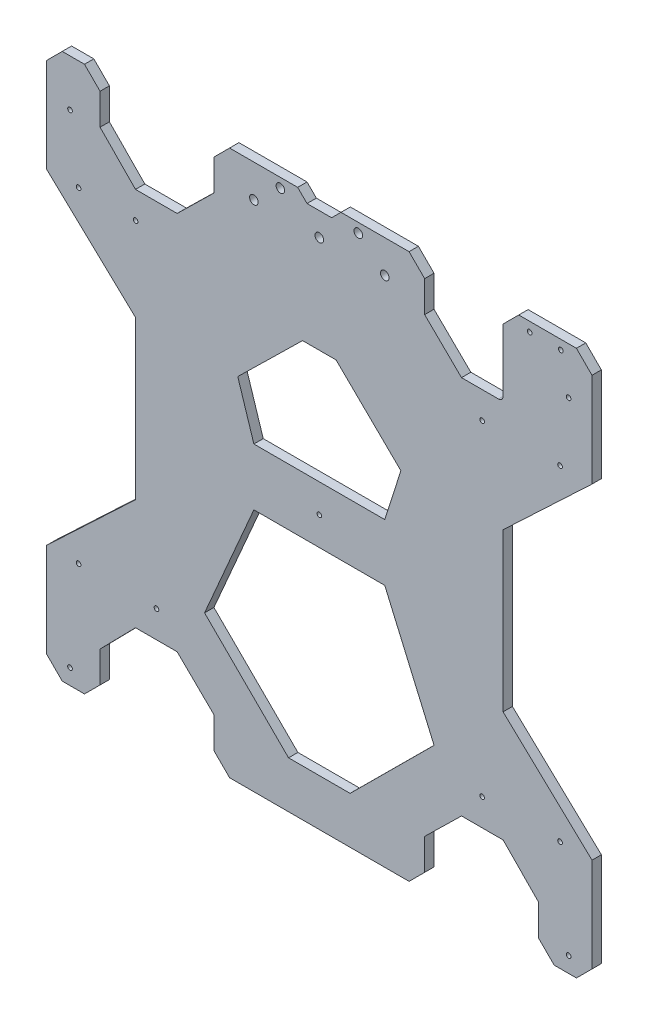
SolidWorks part; units mm, degrees
material "6063-T5"
ref_plane "Piano frontale" through (0, 0, 0) normal (0, 0, 1) x (1, 0, 0)
ref_plane "Piano superiore" through (0, 0, 0) normal (0, 1, 0) x (1, 0, 0)
ref_plane "Piano destro" through (0, 0, 0) normal (1, 0, 0) x (0, 0, -1)
sketch "Schizzo13" plane through (0, 0, 0) normal (0, 0, 1) x (1, 0, 0)
  line L0 (175, 350) -> (175, 0) construction
  line L1 (10, 0) -> (24.282, 0)
  line L2 (0, 279.5) -> (57.0808, 225.6111)
  line L3 (217, 193.2869) -> (227.343, 225.6111)
  line L4 (133, 193.2869) -> (217, 193.2869)
  line L5 (350, 175) -> (0, 175) construction
  line L6 (-60.1887, 10) -> (461.2643, 10) construction
  line L7 (279.5, 279.5) -> (279.5, 175) construction
  line L8 (-12.961, 344) -> (386.8832, 344) construction
  line L9 (-12.961, 329) -> (386.8832, 329) construction
  line L10 (161.1089, 350) -> (167.1089, 344)
  line L11 (279.5, 70.5) -> (175, 70.5) construction
  line L12 (70.5, 70.5) -> (175, 70.5) construction
  line L13 (167.1089, 344) -> (182.8911, 344)
  line L14 (57.0808, 279.5) -> (57.0808, 175) construction
  line L15 (57.0808, 279.5) -> (175, 279.5) construction
  line L16 (175, 279.5) -> (329.5, 279.5) construction
  line L17 (329.5, 70.5) -> (329.5, 279.5) construction
  line L18 (20.5, 70.5) -> (329.5, 70.5) construction
  line L19 (20.5, 70.5) -> (20.5, 279.5) construction
  line L20 (175, 279.5) -> (20.5, 279.5) construction
  line L21 (15, -40.9714) -> (15, 408.5301) construction
  line L22 (335, -40.9714) -> (335, 408.5301) construction
  line L23 (-12.961, 320) -> (386.8832, 320) construction
  line L24 (10, 0) -> (0, 10)
  line L25 (340, 0) -> (350, 10)
  line L26 (107.4046, 340) -> (107.4046, 320)
  line L27 (107.4046, 320) -> (83.7454, 296.8073)
  line L28 (57.0808, 279.5) -> (20.5, 279.5) construction
  line L29 (57.0174, 296.8073) -> (34.282, 320)
  line L30 (83.7454, 296.8073) -> (57.0174, 296.8073)
  line L31 (34.282, 320) -> (34.282, 340)
  line L32 (24.282, 350) -> (10, 350)
  line L33 (133, 193.2869) -> (122.657, 225.6111)
  line L34 (57.0808, 279.5) -> (57.0808, 350) construction
  line L35 (164.2491, 266.3832) -> (185.7509, 266.3832)
  line L36 (122.657, 225.6111) -> (164.2491, 266.3832)
  line L37 (57.0808, 225.6111) -> (57.0808, 175)
  line L38 (227.343, 225.6111) -> (185.7509, 266.3832)
  line L39 (292.9192, 225.6111) -> (292.9192, 124.3889)
  line L40 (350, 279.5) -> (292.9192, 225.6111)
  line L41 (188.8911, 350) -> (182.8911, 344)
  line L42 (117.4046, 350) -> (161.1089, 350)
  line L44 (292.9826, 299.8073) -> (292.9826, 340)
  line L46 (117.4046, 0) -> (232.5954, 0)
  line L47 (266.2546, 296.8073) -> (289.9826, 296.8073)
  line L48 (242.5954, 320) -> (266.2546, 296.8073)
  line L49 (242.5954, 340) -> (242.5954, 320)
  line L50 (350, 70.5) -> (292.9192, 124.3889)
  line L53 (350, 10) -> (350, 70.5)
  line L55 (315.718, 30) -> (315.718, 10)
  line L56 (292.9826, 53.1927) -> (315.718, 30)
  line L57 (266.2546, 53.1927) -> (292.9826, 53.1927)
  line L58 (242.5954, 30) -> (266.2546, 53.1927)
  line L59 (242.5954, 10) -> (242.5954, 30)
  line L60 (107.4046, 10) -> (107.4046, 30)
  line L61 (107.4046, 30) -> (83.7454, 53.1927)
  line L62 (83.7454, 53.1927) -> (57.0174, 53.1927)
  line L63 (57.0174, 53.1927) -> (34.282, 30)
  line L64 (34.282, 30) -> (34.282, 10)
  line L66 (0, 10) -> (0, 70.5)
  line L69 (0, 70.5) -> (57.0808, 124.3889)
  line L70 (57.0808, 124.3889) -> (57.0808, 175)
  line L71 (0, 279.5) -> (0, 340)
  line L72 (188.8911, 350) -> (232.5954, 350)
  line L73 (302.9826, 350) -> (340, 350)
  line L74 (350, 279.5) -> (350, 340)
  line L75 (325.718, 0) -> (340, 0)
  line L76 (24.282, 0) -> (34.282, 10)
  line L77 (117.4046, 0) -> (107.4046, 10)
  line L78 (232.5954, 0) -> (242.5954, 10)
  line L79 (315.718, 10) -> (325.718, 0)
  line L80 (10, 350) -> (0, 340)
  line L81 (24.282, 350) -> (34.282, 340)
  line L82 (107.4046, 340) -> (117.4046, 350)
  line L83 (232.5954, 350) -> (242.5954, 340)
  line L84 (292.9826, 340) -> (302.9826, 350)
  line L85 (340, 350) -> (350, 340)
  line L86 (133, 156.7131) -> (101.3482, 83.6168)
  line L87 (101.3482, 83.6168) -> (155.2542, 30)
  line L88 (155.2542, 30) -> (194.7458, 30)
  line L89 (133, 156.7131) -> (217, 156.7131)
  line L90 (248.6518, 83.6168) -> (194.7458, 30)
  line L91 (217, 156.7131) -> (248.6518, 83.6168)
  circle A0 centre (15, 320) radius 1.5
  circle A1 centre (20.5, 279.5) radius 1.5
  circle A2 centre (57.0808, 279.5) radius 1.5
  circle A3 centre (175, 175) radius 1.5
  arc A4 (289.9826, 296.8073) -> (292.9826, 299.8073) centre (289.9826, 299.8073) ccw
  circle A5 centre (20.5, 70.5) radius 1.5
  circle A6 centre (200, 344) radius 2.75
  circle A7 centre (150, 344) radius 2.75
  circle A8 centre (175, 329) radius 2.75
  circle A9 centre (217, 329) radius 2.75
  circle A10 centre (133, 329) radius 2.75
  circle A11 centre (70.5, 70.5) radius 1.5
  circle A12 centre (279.5, 70.5) radius 1.5
  circle A13 centre (329.5, 70.5) radius 1.5
  circle A14 centre (335, 10) radius 1.5
  circle A15 centre (15, 10) radius 1.5
  circle A16 centre (279.5, 279.5) radius 1.5
  circle A17 centre (329.5, 279.5) radius 1.5
  circle A18 centre (335, 320) radius 1.5
  circle A19 centre (310, 344) radius 1.5
  circle A20 centre (330, 344) radius 1.5
  point P7 (175, 175)
  point P25 (175, 344)
  point P30 (175, 329)
  point P41 (175, 175)
  point P43 (329.5, 175)
  point P46 (15, 320)
  point P54 (335, 320)
  point P55 (335, 10)
  point P56 (15, 10)
  point P57 (15, 320)
  point P58 (335, 320)
  point P59 (15, 10)
  point P60 (335, 10)
  point P93 (292.9826, 296.8073)
  point P108 (175, 344)
  point P155 (175, 156.7131)
  point P156 (175, 30)
  dimension "D5" = 42
  dimension "D6" = 5.5
  dimension "D7" = 25
  dimension "D8" = 15
  dimension "D10" = 154.5
  dimension "D3" = 104.5
  dimension "D17" = 20
  dimension "D2" = 3
  dimension "D4" = 104.5
  dimension "D11" = 104.5
  dimension "D15" = 310
  dimension "D16" = 320
extrude "Estrusione-Estrusione2" add sketch "Schizzo13" against normal blind 6
sketch "Schizzo14" plane through (0, 0, 0) normal (0, 0, 1) x (1, 0, 0)
  line L0 (350, 350.0234) -> (0, 350.0234)
  line L2 (0, 350.0234) -> (0, 0)
  line L3 (0, 0) -> (350, 0)
  line L4 (117.4046, 0) -> (232.5954, 0) construction
  line L5 (175, 344) -> (175, 0) construction
  line L6 (350, 350.0234) -> (350, 0)
  line L7 (182.8911, 344) -> (167.1089, 344) construction
  circle A0 centre (175, 223.4858) radius 4.4409
  circle A1 centre (175, 78.9698) radius 4.6362
  dimension "D1" = 350.0234
  dimension "D2" = 350
sketch "Schizzo15" plane through (0, 0, 0) normal (0, 0, 1) x (1, 0, 0)
  text T0 "HackerBot" font "Lobster 1.4" height 14
